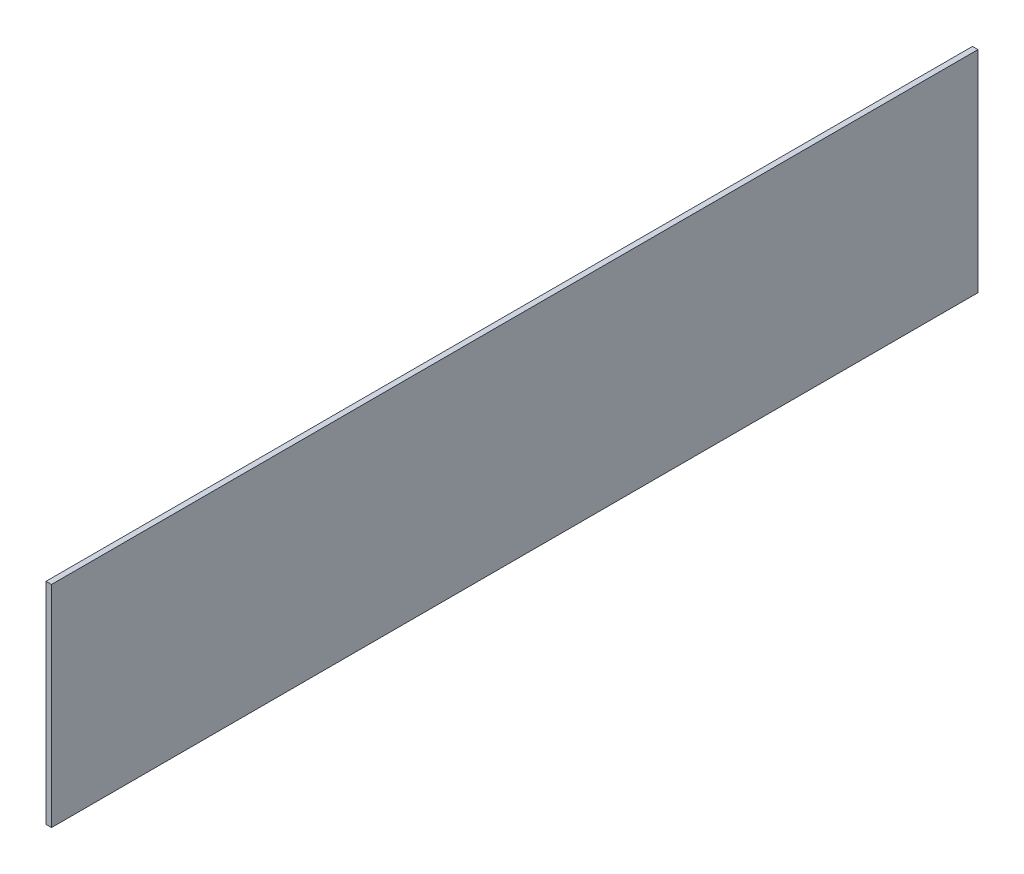
SolidWorks part; units mm, degrees
note: The reader was unsure of these and kept them because the rebuilt part matched: thickness of "Базовая кромка1", "Листовой металл3".
material "AISI 304"
ref_plane "Спереди" through (0, 0, 0) normal (0, 0, 1) x (1, 0, 0)
ref_plane "Сверху" through (0, 0, 0) normal (0, 1, 0) x (1, 0, 0)
ref_plane "Справа" through (0, 0, 0) normal (1, 0, 0) x (0, 0, -1)
sketch "Эскиз1" plane through (0, 0, 0) normal (1, 0, 0) x (0, 0, -1)
  line L1 (-253, 57.5) -> (253, 57.5)
  line L2 (-253, 57.5) -> (-253, -57.5)
  line L3 (-253, -57.5) -> (253, -57.5)
  line L4 (253, 57.5) -> (253, -57.5)
  line L5 (-253, 57.5) -> (253, -57.5) construction
  line L6 (-253, -57.5) -> (253, 57.5) construction
  point P0 (0, 0)
  dimension "D1" = 506
  dimension "D2" = 115
base flange "Базовая кромка1" sketch "Эскиз1" thickness 3 reverse thickness direction no parameters "D1"=4
sketch "Сгиб-Линии1" plane through (0, 0, 0) normal (0, 1, 0) x (1, 0, 0)
sketch "Граничная рамка1" plane through (0, 0, 0) normal (0, 1, 0) x (1, 0, 0)
sheet metal parameters "Листовой металл3" thickness 3 parameters "D1"=4
flat pattern "Развертка3" [suppressed]
sketch "Сгиб-Линии2" plane through (0, 0, 0) normal (0, 1, 0) x (1, 0, 0)
sketch "Граничная рамка2" [suppressed] plane through (0, 0, 0) normal (0, 1, 0) x (1, 0, 0)
